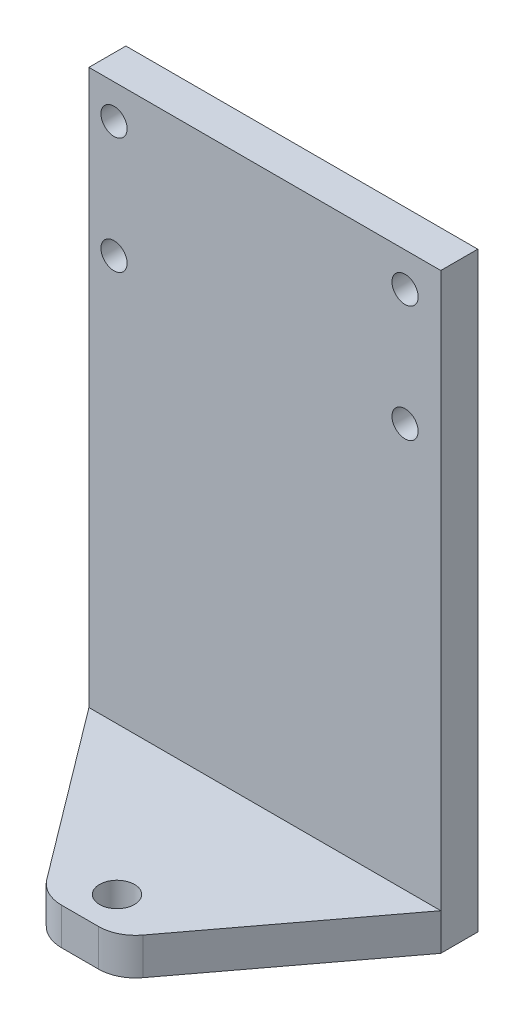
SolidWorks part; units mm, degrees
material "6061 Alloy"
ref_plane "Front" through (0, 0, 0) normal (0, 0, 1) x (1, 0, 0)
ref_plane "Top" through (0, 0, 0) normal (0, 1, 0) x (1, 0, 0)
ref_plane "Right" through (0, 0, 0) normal (1, 0, 0) x (0, 0, -1)
sketch "Sketch1" plane through (0, 0, 0) normal (0, 0, 1) x (1, 0, 0)
  line L1 (-30.226, -50.8) -> (30.226, -50.8)
  line L2 (-30.226, -50.8) -> (-30.226, 50.8)
  line L3 (-30.226, 50.8) -> (30.226, 50.8)
  line L4 (30.226, -50.8) -> (30.226, 50.8)
  line L5 (-30.226, -50.8) -> (30.226, 50.8) construction
  line L6 (-30.226, 50.8) -> (30.226, -50.8) construction
  point P0 (0, 0)
  dimension "D1" = 60.452
  dimension "D2" = 101.6
extrude "Boss-Extrude1" add sketch "Sketch1" along normal mid plane 6.35
sketch "Sketch2" plane through (0, -50.8, 0) normal (0, -1, 0) x (1, 0, 0)
  line L0 (-30.226, 3.175) -> (30.226, 3.175) construction
  line L1 (-30.226, -3.175) -> (30.226, -3.175)
  line L2 (-30.226, -3.175) -> (-30.226, 53.975)
  line L3 (-30.226, 53.975) -> (30.226, 53.975)
  line L4 (30.226, -3.175) -> (30.226, 53.975)
  dimension "D1" = 50.8
extrude "Boss-Extrude2" add sketch "Sketch2" against normal blind 6.35
sketch "Sketch3" plane through (0, 0, -3.175) normal (0, 0, -1) x (-1, 0, 0)
  circle A0 centre (-24.0864, 44.925) radius 2.25 construction
  circle A1 centre (-24.0864, 24.925) radius 2.25 construction
  circle A2 centre (25.9136, 24.925) radius 2.25 construction
  circle A3 centre (25.9136, 44.925) radius 2.25 construction
  circle A4 centre (-24.0864, 44.925) radius 2.25
  circle A5 centre (-24.0864, 24.925) radius 2.25
  circle A6 centre (25.9136, 24.925) radius 2.25
  circle A7 centre (25.9136, 44.925) radius 2.25
extrude "Cut-Extrude1" cut sketch "Sketch3" against normal through all
sketch "Sketch4" plane through (0, -44.45, 0) normal (0, 1, 0) x (1, 0, 0)
  line L0 (-30.226, -53.975) -> (-30.226, -3.175) construction
  line L1 (30.226, -53.975) -> (-30.226, -53.975) construction
  circle A0 centre (0, -28.575) radius 3
  point P4 (-30.226, -28.575)
  point P7 (0, -53.975)
  dimension "D1" = 6
extrude "Cut-Extrude2" cut sketch "Sketch4" against normal through all
sketch "Sketch5" plane through (0, -44.45, 0) normal (0, 1, 0) x (1, 0, 0)
  line L0 (-30.226, -3.175) -> (-6.35, -34.925)
  line L1 (-6.35, -34.925) -> (6.35, -34.925)
  line L2 (6.35, -34.925) -> (30.226, -3.175)
  line L3 (30.226, -3.175) -> (30.226, -53.975)
  line L4 (30.226, -53.975) -> (-30.226, -53.975)
  line L5 (-30.226, -53.975) -> (-30.226, -3.175)
  line L6 (0, -34.925) -> (0, -53.975) construction
  circle A0 centre (0, -28.575) radius 3 construction
  dimension "D1" = 6.35
  dimension "D2" = 12.7
extrude "Cut-Extrude3" cut sketch "Sketch5" against normal through all
fillet "Fillet1" radius 6.35 2 edges at (6.35, -47.625, 34.925) (-6.35, -47.625, 34.925)
